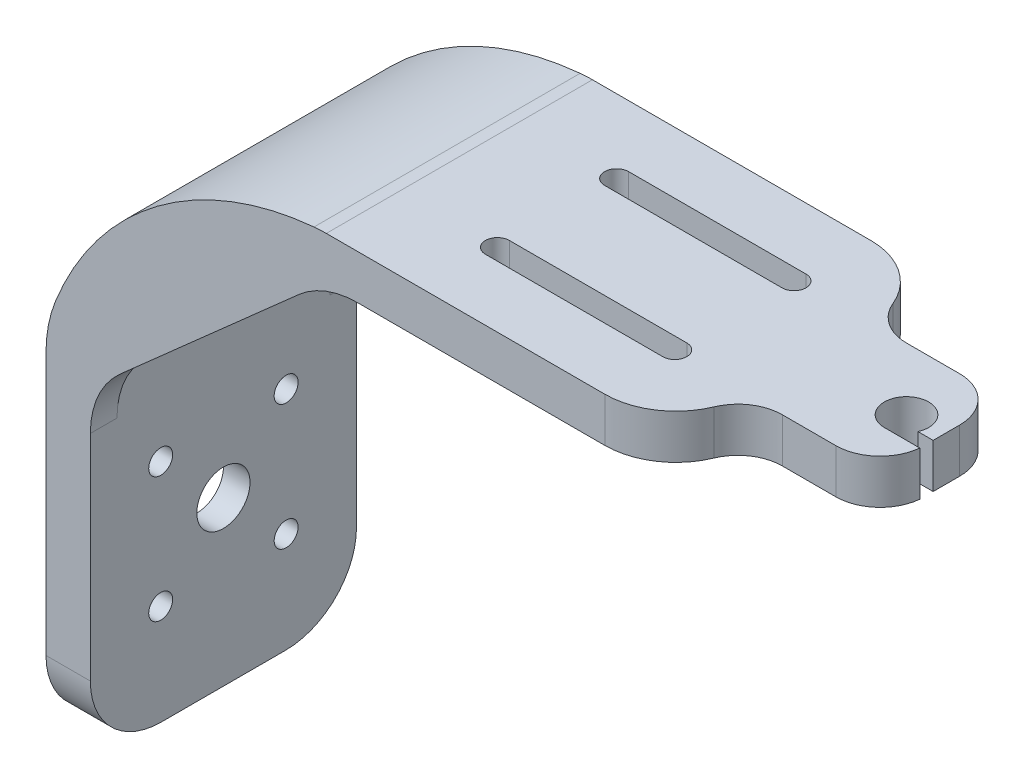
SolidWorks part; units mm, degrees
material "ABS"
ref_plane "Alzado" through (0, 0, 0) normal (0, 0, 1) x (1, 0, 0)
ref_plane "Planta" through (0, 0, 0) normal (0, 1, 0) x (1, 0, 0)
ref_plane "Vista lateral" through (0, 0, 0) normal (1, 0, 0) x (0, 0, -1)
sketch "Croquis1" plane through (0, 0, 0) normal (0, 0, 1) x (1, 0, 0)
  line L0 (0, 0) -> (0, 5)
  line L1 (0, 5) -> (-40, 5)
  line L2 (-40, 5) -> (-71, -20) construction
  line L3 (-71, -20) -> (-71, -60)
  line L4 (-71, -60) -> (-66, -60)
  line L5 (-66, -60) -> (-66, -20.5357)
  line L6 (-66, -20.5357) -> (-40.5357, 0) construction
  line L7 (-40.5357, 0) -> (0, 0)
  line L8 (-53.2679, -10.2679) -> (-37.574, -29.7282) construction
  arc A0 (-40, 5) -> (-71, -20) centre (-37.574, -29.7282) ccw
  arc A1 (-40.5357, 0) -> (-66, -20.5357) centre (-37.574, -29.7282) ccw
  dimension "D1" = 5
  dimension "D2" = 31
  dimension "D4" = 5
  dimension "D5" = 40
  dimension "D6" = 40
  dimension "D7" = 25
  dimension "D8" = 25
extrude "Saliente-Extruir1" add sketch "Croquis1" along normal blind 30
sketch "Croquis2" plane through (0, 5, 0) normal (0, 1, 0) x (1, 0, 0)
  line L0 (0, -30) -> (0, 0) construction
  line L1 (-18.4, -15) -> (-18.4, -12) construction
  line L2 (-18.4, -12) -> (-11.4, -12) construction
  line L4 (-11.4, -18) -> (-25.4, -18) construction
  line L6 (-25.4, -12) -> (-18.4, -12) construction
  line L7 (-18.4, -15) -> (-18.4, -8.28) construction
  line L8 (-18.4, -8.28) -> (-18.4, -6.93) construction
  line L9 (-18.4, -6.93) -> (-8.4, -6.93)
  line L11 (-8.4, -9.63) -> (-28.4, -9.63)
  line L13 (-28.4, -6.93) -> (-18.4, -6.93)
  line L14 (-18.4, -15) -> (-21.0577, -15) construction
  line L22 (0, -15) -> (-18.4, -15) construction
  line L23 (-8.4, -20.37) -> (-28.4, -20.37)
  line L24 (-18.4, -23.07) -> (-8.4, -23.07)
  line L25 (-28.4, -23.07) -> (-18.4, -23.07)
  circle A0 centre (-18.4, -15) radius 18.4 construction
  arc A1 (-25.4, -18) -> (-25.4, -12) centre (-25.4, -15) cw construction
  arc A2 (-11.4, -18) -> (-11.4, -12) centre (-11.4, -15) ccw construction
  arc A3 (-8.4, -9.63) -> (-8.4, -6.93) centre (-8.4, -8.28) ccw
  arc A4 (-28.4, -9.63) -> (-28.4, -6.93) centre (-28.4, -8.28) cw
  arc A9 (-8.4, -20.37) -> (-8.4, -23.07) centre (-8.4, -21.72) cw
  arc A10 (-28.4, -20.37) -> (-28.4, -23.07) centre (-28.4, -21.72) ccw
  dimension "D1" = 36.8
  dimension "D5" = 3
  dimension "D6" = 3
  dimension "D11" = 1.35
  dimension "D12" = 1.35
  dimension "D2" = 18.4
  dimension "D3" = 3
  dimension "D4" = 6
  dimension "D7" = 7
  dimension "D8" = 7
  dimension "D9" = 6.72
  dimension "D10" = 2.7
  dimension "D13" = 10
  dimension "D14" = 10
extrude "Cortar-Extruir1" cut sketch "Croquis2" against normal up to vertex (5 mm away) up to point (0, 0, 30)
sketch "Croquis3" plane through (0, 0, 0) normal (0, -1, 0) x (1, 0, 0)
  line L0 (0, 30) -> (0, 0) construction
  line L5 (-28.4, 9.63) -> (-8.4, 9.63) construction
  line L6 (-33.4, 27.5) -> (-3.4, 27.5)
  line L7 (-33.4, 27.5) -> (-33.4, 2.5)
  line L8 (-33.4, 2.5) -> (-3.4, 2.5)
  line L9 (-3.4, 27.5) -> (-3.4, 2.5)
  line L10 (-33.4, 27.5) -> (-3.4, 2.5) construction
  line L11 (-33.4, 2.5) -> (-3.4, 27.5) construction
  line L12 (0, 15) -> (-18.4, 15) construction
  line L13 (-18.4, 15) -> (-18.4, 9.63) construction
  point P0 (-18.4, 15)
  dimension "D1" = 25
  dimension "D2" = 30
extrude "Cortar-Extruir2" cut sketch "Croquis3" against normal blind 2
sketch "Croquis4" plane through (-71, 0, 0) normal (-1, 0, 0) x (0, 0, 1)
  line L0 (30, -60) -> (0, -60) construction
  line L1 (15, -41.6) -> (21.5109, -41.6) construction
  line L3 (22.0711, -34.5289) -> (15, -41.6) construction
  circle A0 centre (15, -41.6) radius 18.4 construction
  circle A1 centre (22.0711, -34.5289) radius 1.35
  circle A2 centre (22.0711, -48.6711) radius 1.35
  circle A3 centre (7.9289, -48.6711) radius 1.35
  circle A4 centre (7.9289, -34.5289) radius 1.35
  circle A5 centre (15, -41.6) radius 3
  point P15 (15, -41.6)
  dimension "D1" = 36.8
  dimension "D5" = 2.7
  dimension "D7" = 6
  dimension "D2" = 18.4
  dimension "D3" = 45
  dimension "D4" = 10
  dimension "D6" = 4
extrude "Cortar-Extruir3" cut sketch "Croquis4" against normal up to vertex (5 mm away) up to point (-66, -60, 30)
sketch "Croquis5" plane through (-71, 0, 0) normal (-1, 0, 0) x (0, 0, 1)
  line L0 (15, -41.6) -> (15, -38.6) construction
  line L1 (2.5, -54.1) -> (27.5, -54.1)
  line L2 (2.5, -54.1) -> (2.5, -29.1)
  line L3 (2.5, -29.1) -> (27.5, -29.1)
  line L4 (27.5, -54.1) -> (27.5, -29.1)
  line L5 (2.5, -54.1) -> (27.5, -29.1) construction
  line L6 (2.5, -29.1) -> (27.5, -54.1) construction
  line L8 (18, -41.6) -> (15, -41.6) construction
  circle A0 centre (15, -41.6) radius 3 construction
  point P0 (15, -41.6)
  dimension "D1" = 25
  dimension "D2" = 25
extrude "Cortar-Extruir4" cut sketch "Croquis5" against normal blind 2
fillet "Redondeo1" radius 15 4 edges at (-40, 5, 15) (-71, -20, 15) (-40.5357, 0, 15) (-66, -20.5357, 15)
fillet "Redondeo2" radius 8 4 edges at (-68.5, -60, 0) (-68.5, -60, 30) (0, 2.5, 0) (0, 2.5, 30)
fillet "Redondeo3" radius 2.7 8 edges at (-70, -54.1, 2.5) (-70, -29.1, 2.5) (-70, -29.1, 27.5) (-70, -54.1, 27.5) (-33.4, 1, 2.5) (-33.4, 1, 27.5) (-3.4, 1, 27.5) (-3.4, 1, 2.5)
sketch "Croquis6" plane through (0, 0, 0) normal (0, -1, 0) x (1, 0, 0)
  line L0 (0, 22) -> (0, 8)
  line L1 (0, 8) -> (15, 8)
  line L2 (15, 8) -> (15, 16)
  line L3 (15, 22) -> (0, 22)
  line L6 (15, 17.5) -> (15, 22)
  line L7 (13.5, 15) -> (13.5, 16) construction
  line L8 (13.5, 16) -> (15, 16) construction
  line L9 (15, 16) -> (13.2913, 16)
  line L10 (13.5, 15) -> (14.5144, 15) construction
  line L11 (11, 17.5) -> (15, 17.5)
  arc A1 (11, 17.5) -> (13.2913, 16) centre (11, 15) ccw
  dimension "D2" = 4
  dimension "D1" = 15
  dimension "D3" = 1
extrude "Saliente-Extruir2" add sketch "Croquis6" against normal up to vertex (5 mm away) up to point (0, 5, 8)
fillet "Redondeo4" radius 5 4 edges at (0, 2.5, 8) (15, 2.5, 8) (15, 2.5, 22) (0, 2.5, 22)
sketch "Croquis7" plane through (-69, 0, 0) normal (-1, 0, 0) x (0, 0, 1)
  line L24 (5.2, -54.1) -> (24.8, -54.1)
  line L25 (2.5, -31.8) -> (2.5, -51.4)
  line L26 (24.8, -29.1) -> (5.2, -29.1)
  line L27 (27.5, -51.4) -> (27.5, -31.8)
  line L28 (5.2, -54.1) -> (24.8, -54.1)
  line L29 (2.5, -31.8) -> (2.5, -51.4)
  line L30 (24.8, -29.1) -> (5.2, -29.1)
  line L31 (27.5, -51.4) -> (27.5, -31.8)
  circle A0 centre (22.0711, -34.5289) radius 1.35
  circle A1 centre (15, -41.6) radius 3
  circle A2 centre (22.0711, -48.6711) radius 1.35
  circle A3 centre (7.9289, -34.5289) radius 1.35
  circle A4 centre (7.9289, -48.6711) radius 1.35
  arc A25 (24.8, -54.1) -> (27.5, -51.4) centre (24.8, -51.4) ccw
  arc A26 (2.5, -51.4) -> (5.2, -54.1) centre (5.2, -51.4) ccw
  arc A27 (5.2, -29.1) -> (2.5, -31.8) centre (5.2, -31.8) ccw
  arc A28 (27.5, -31.8) -> (24.8, -29.1) centre (24.8, -31.8) ccw
  arc A29 (24.8, -54.1) -> (27.5, -51.4) centre (24.8, -51.4) ccw
  arc A30 (2.5, -51.4) -> (5.2, -54.1) centre (5.2, -51.4) ccw
  arc A31 (5.2, -29.1) -> (2.5, -31.8) centre (5.2, -31.8) ccw
  arc A32 (27.5, -31.8) -> (24.8, -29.1) centre (24.8, -31.8) ccw
  dimension "D1" = 0
sketch "Croquis8" plane through (0, 2, 0) normal (0, -1, 0) x (1, 0, 0)
  line L24 (-3.4, 5.2) -> (-3.4, 24.8)
  line L25 (-30.7, 2.5) -> (-6.1, 2.5)
  line L26 (-33.4, 24.8) -> (-33.4, 5.2)
  line L27 (-6.1, 27.5) -> (-30.7, 27.5)
  line L28 (-3.4, 5.2) -> (-3.4, 24.8)
  line L29 (-30.7, 2.5) -> (-6.1, 2.5)
  line L30 (-33.4, 24.8) -> (-33.4, 5.2)
  line L31 (-6.1, 27.5) -> (-30.7, 27.5)
  line L36 (-28.4, 20.37) -> (-8.4, 20.37)
  line L37 (-8.4, 23.07) -> (-28.4, 23.07)
  line L38 (-28.4, 20.37) -> (-8.4, 20.37)
  line L39 (-8.4, 23.07) -> (-28.4, 23.07)
  line L46 (-28.4, 6.93) -> (-8.4, 6.93)
  line L47 (-8.4, 9.63) -> (-28.4, 9.63)
  line L48 (-28.4, 6.93) -> (-8.4, 6.93)
  line L49 (-8.4, 9.63) -> (-28.4, 9.63)
  arc A20 (-3.4, 24.8) -> (-6.1, 27.5) centre (-6.1, 24.8) ccw
  arc A21 (-6.1, 2.5) -> (-3.4, 5.2) centre (-6.1, 5.2) ccw
  arc A22 (-33.4, 5.2) -> (-30.7, 2.5) centre (-30.7, 5.2) ccw
  arc A23 (-30.7, 27.5) -> (-33.4, 24.8) centre (-30.7, 24.8) ccw
  arc A24 (-3.4, 24.8) -> (-6.1, 27.5) centre (-6.1, 24.8) ccw
  arc A25 (-6.1, 2.5) -> (-3.4, 5.2) centre (-6.1, 5.2) ccw
  arc A26 (-33.4, 5.2) -> (-30.7, 2.5) centre (-30.7, 5.2) ccw
  arc A27 (-30.7, 27.5) -> (-33.4, 24.8) centre (-30.7, 24.8) ccw
  arc A30 (-8.4, 20.37) -> (-8.4, 23.07) centre (-8.4, 21.72) ccw
  arc A31 (-28.4, 23.07) -> (-28.4, 20.37) centre (-28.4, 21.72) ccw
  arc A32 (-8.4, 20.37) -> (-8.4, 23.07) centre (-8.4, 21.72) ccw
  arc A33 (-28.4, 23.07) -> (-28.4, 20.37) centre (-28.4, 21.72) ccw
  arc A38 (-8.4, 6.93) -> (-8.4, 9.63) centre (-8.4, 8.28) ccw
  arc A39 (-28.4, 9.63) -> (-28.4, 6.93) centre (-28.4, 8.28) ccw
  arc A40 (-8.4, 6.93) -> (-8.4, 9.63) centre (-8.4, 8.28) ccw
  arc A41 (-28.4, 9.63) -> (-28.4, 6.93) centre (-28.4, 8.28) ccw
  dimension "D1" = 0
  dimension "D2" = 0
  dimension "D3" = 0
sketch "Croquis9" plane through (0, 0, 30) normal (0, 0, 1) x (1, 0, 0)
  line L0 (-66, -23.3235) -> (-39.6613, 0)
  arc A9 (-39.6613, 0) -> (-41.766, -0.1484) centre (-39.6613, -15) ccw
  arc A10 (-41.766, -0.1484) -> (-64.5385, -16.8652) centre (-37.574, -29.7282) ccw
  arc A11 (-64.5385, -16.8652) -> (-66, -23.3235) centre (-51, -23.3235) ccw
  arc A12 (-39.6613, 0) -> (-41.766, -0.1484) centre (-39.6613, -15) ccw
  arc A13 (-41.766, -0.1484) -> (-64.5385, -16.8652) centre (-37.574, -29.7282) ccw
  arc A14 (-64.5385, -16.8652) -> (-66, -23.3235) centre (-51, -23.3235) ccw
  dimension "D1" = 0
extrude "Saliente-Extruir3" add sketch "Croquis9" against normal blind 3
extrude "Saliente-Extruir4" add sketch "Croquis9<2>" along normal blind 3 from surface starting at face at (-49.3269, -13.4677, 0)
sketch "Croquis9<2>" plane through (0, 0, 30) normal (0, 0, 1) x (1, 0, 0) same geometry as "Croquis9"
fillet "Redondeo5" radius 10 4 edges at (-39.6613, 0, 1.5) (-66, -23.3235, 1.5) (-39.6613, 0, 28.5) (-66, -23.3235, 28.5)
